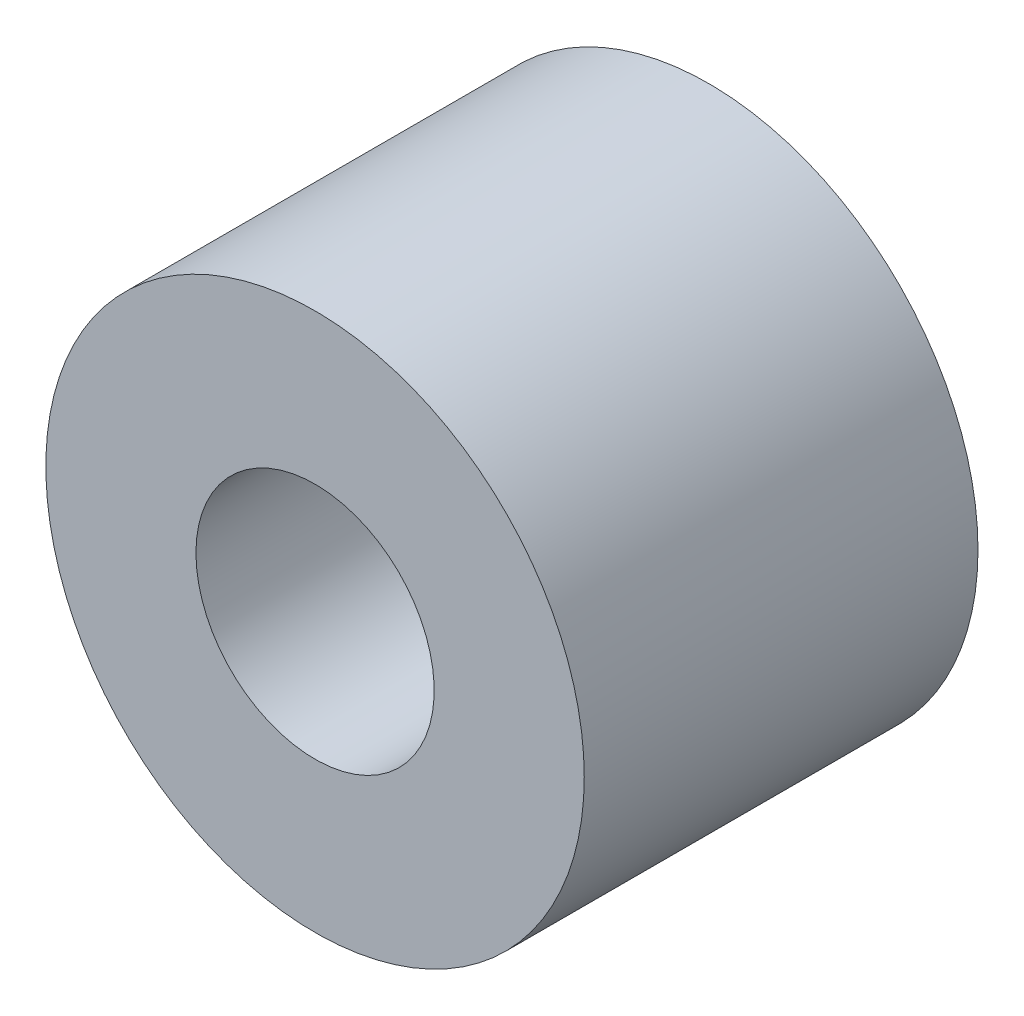
SolidWorks part; units mm, degrees
material "PLA Plus"
ref_plane "Front Plane" through (0, 0, 0) normal (0, 0, 1) x (1, 0, 0)
ref_plane "Top Plane" through (0, 0, 0) normal (0, 1, 0) x (1, 0, 0)
ref_plane "Right Plane" through (0, 0, 0) normal (1, 0, 0) x (0, 0, -1)
sketch "Sketch1" plane through (0, 0, 0) normal (0, 0, 1) x (1, 0, 0)
  circle A0 centre (0, 0) radius 2.2479
  circle A1 centre (0, 0) radius 5.08
  dimension "D1" = 10.16
  dimension "D2" = 4.4958
extrude "Boss-Extrude1" add sketch "Sketch1" along normal up to surface (7.4295 mm away)
